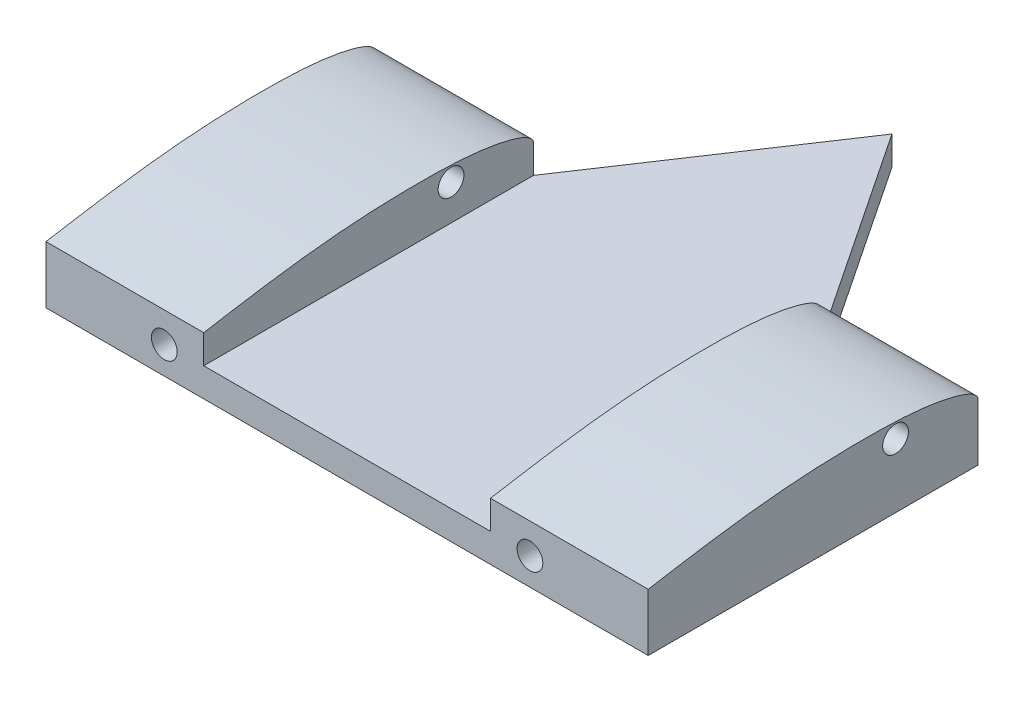
SolidWorks part; units mm, degrees
note: The reader was unsure of these and kept them because the rebuilt part matched: shared geometry of "Schizzo13<3>".
ref_plane "Piano frontale" through (0, 0, 0) normal (0, 0, 1) x (1, 0, 0)
ref_plane "Piano superiore" through (0, 0, 0) normal (0, 1, 0) x (1, 0, 0)
ref_plane "Piano destro" through (0, 0, 0) normal (1, 0, 0) x (0, 0, -1)
curve "Curva2"
  spline degree 3 poles (0, 0.1586, 228.4222) (0, -0.0487, 230.3931) (0, 0.2265, 228.4621) (0, 0.5086, 226.913) (0, 1.1462, 223.2123) (0, 1.931, 218.7267) (0, 2.9273, 212.8543) (0, 3.9498, 206.059) (0, 5.2727, 198.3155) (0, 6.561, 189.7964) (0, 7.9418, 180.47) (0, 9.3069, 170.5242) (0, 10.6253, 160.0699) (0, 11.8511, 149.2161) (0, 12.9346, 138.0666) (0, 13.8481, 126.7243) (0, 14.5595, 115.2867) (0, 15.0727, 103.8577) (0, 15.3886, 92.5492) (0, 15.5156, 81.4816) (0, 15.4486, 70.7769) (0, 15.1745, 60.5512) (0, 14.684, 50.9063) (0, 13.9467, 41.9272) (0, 12.97, 33.6788) (0, 11.7653, 26.2174) (0, 10.3812, 19.5949) (0, 8.87, 13.8689) (0, 7.2805, 9.0905) (0, 5.6287, 5.3083) (0, 3.8993, 2.5106) (0, 2.1212, 0.7476) (0, 0.7292, 0.0287) (0, -0.3776, -0.0196) (0, -1.5746, 0.4553) (0, -2.6365, 2.4153) (0, -3.7172, 5.2419) (0, -4.5344, 9.2662) (0, -5.1496, 14.3761) (0, -5.5312, 20.6192) (0, -5.7638, 27.933) (0, -5.8709, 36.2454) (0, -5.8469, 45.4468) (0, -5.721, 55.4256) (0, -5.4718, 66.0577) (0, -5.0939, 77.2256) (0, -4.5435, 88.8224) (0, -3.8205, 100.7584) (0, -2.962, 112.9458) (0, -2.0157, 125.2822) (0, -1.0562, 137.6465) (0, -0.1474, 149.8969) (0, 0.6495, 161.8774) (0, 1.2784, 173.4199) (0, 1.6866, 184.3415) (0, 1.8102, 194.4306) (0, 1.6774, 203.4894) (0, 1.3775, 211.306) (0, 0.9882, 217.8619) (0, 0.6308, 222.8142) (0, 0.284, 226.7967) (0, 0.1586, 228.4222) (0, -0.0487, 230.3931) (0, 0.2265, 228.4621) knots -0.014202 -0.006329 -0.001589 0 0.001576 0.006211 0.01368 0.023764 0.036307 0.051658 0.068045 0.086769 0.107053 0.128647 0.151303 0.174786 0.19886 0.223309 0.247929 0.272522 0.296848 0.320648 0.343669 0.365658 0.3864 0.405741 0.423561 0.439779 0.454311 0.467034 0.477831 0.486643 0.493542 0.498786 0.50271 0.50309 0.505896 0.510322 0.516831 0.525521 0.536535 0.549945 0.565696 0.583577 0.603379 0.624844 0.647727 0.671743 0.696673 0.722357 0.748609 0.77521 0.801891 0.828329 0.854175 0.879074 0.902636 0.924421 0.943939 0.960827 0.974827 0.985798 0.993671 0.998411 1 1.001576 1.006211 1.01368 periodic
sketch "Schizzo1" plane through (0, 0, 0) normal (1, 0, 0) x (0, 0, -1)
  spline S1 degree 3 poles (-228.4621, 0.2265) (-230.3931, -0.0487) (-228.4222, 0.1586) (-226.7967, 0.284) (-222.8142, 0.6308) (-217.8619, 0.9882) (-211.306, 1.3775) (-203.4894, 1.6774) (-194.4306, 1.8102) (-184.3415, 1.6866) (-173.4199, 1.2784) (-161.8774, 0.6495) (-149.8969, -0.1474) (-137.6465, -1.0562) (-125.2822, -2.0157) (-112.9458, -2.962) (-100.7584, -3.8205) (-88.8224, -4.5435) (-77.2256, -5.0939) (-66.0577, -5.4718) (-55.4256, -5.721) (-45.4468, -5.8469) (-36.2454, -5.8709) (-27.933, -5.7638) (-20.6192, -5.5312) (-14.3761, -5.1496) (-9.2662, -4.5344) (-5.2419, -3.7172) (-2.4153, -2.6365) (-0.4553, -1.5746) (0.0196, -0.3776) (-0.0287, 0.7292) (-0.7476, 2.1212) (-2.5106, 3.8993) (-5.3083, 5.6287) (-9.0905, 7.2805) (-13.8689, 8.87) (-19.5949, 10.3812) (-26.2174, 11.7653) (-33.6788, 12.97) (-41.9272, 13.9467) (-50.9063, 14.684) (-60.5512, 15.1745) (-70.7769, 15.4486) (-81.4816, 15.5156) (-92.5492, 15.3886) (-103.8577, 15.0727) (-115.2867, 14.5595) (-126.7243, 13.8481) (-138.0666, 12.9346) (-149.2161, 11.8511) (-160.0699, 10.6253) (-170.5242, 9.3069) (-180.47, 7.9418) (-189.7964, 6.561) (-198.3155, 5.2727) (-206.059, 3.9498) (-212.8543, 2.9273) (-218.7267, 1.931) (-223.2123, 1.1462) (-226.913, 0.5086) (-228.4621, 0.2265) (-230.3931, -0.0487) (-228.4222, 0.1586) knots -0.01368 -0.006211 -0.001576 0 0.001589 0.006329 0.014202 0.025173 0.039173 0.056061 0.075579 0.097364 0.120926 0.145825 0.171671 0.198109 0.22479 0.251391 0.277643 0.303327 0.328257 0.352273 0.375156 0.396621 0.416423 0.434304 0.450055 0.463465 0.474479 0.483169 0.489678 0.494104 0.49691 0.49729 0.501214 0.506458 0.513357 0.522169 0.532966 0.545689 0.560221 0.576439 0.594259 0.6136 0.634342 0.656331 0.679352 0.703152 0.727478 0.752071 0.776691 0.80114 0.825214 0.848697 0.871353 0.892947 0.913231 0.931955 0.948342 0.963693 0.976236 0.98632 0.993789 0.998424 1 1.001589 1.006329 1.014202 only from (-230, 0) to (-230, 0)
ref_plane "Piano1" through (100, 0, 0) normal (1, 0, 0) x (0, 0, -1)
sketch "Schizzo3" plane through (0, 0, 0) normal (0, 1, 0) x (1, 0, 0)
  line L0 (-100, 115) -> (0, 265)
  line L1 (-100, 115) -> (100, 115) construction
  line L2 (-100, 115) -> (-100, -115)
  line L3 (-100, -115) -> (100, -115)
  line L4 (100, 115) -> (100, -115)
  line L5 (-100, 115) -> (100, -115) construction
  line L6 (-100, -115) -> (100, 115) construction
  line L7 (0, 265) -> (100, 115)
  line L8 (0, 265) -> (0, 115) construction
  point P0 (0, 0)
  dimension "D1" = 200
  dimension "D2" = 230
  dimension "D3" = 150
extrude "Estrusione-Estrusione1" add sketch "Schizzo3" along normal blind 10
sketch "Schizzo4" plane through (0, 0, 0) normal (0, 1, 0) x (1, 0, 0)
  line L1 (-100, 115) -> (-210, 115)
  line L2 (-100, 115) -> (-100, -115)
  line L3 (-100, -115) -> (-210, -115)
  line L4 (-210, 115) -> (-210, -115)
  dimension "D1" = 110
extrude "Estrusione-Estrusione2" add sketch "Schizzo4" along normal blind 30
mirror "Specchia1" about plane through (0, 0, 0) normal (1, 0, 0) of "Estrusione-Estrusione2"
sketch "Schizzo2" plane through (100, 0, 0) normal (1, 0, 0) x (0, 0, -1)
  line L0 (-115, 30) -> (115, 30) construction
  line L1 (115, 30) -> (115, 38.7777) construction
  line L2 (115, 30) -> (115, 0) construction
  line L4 (115, 10) -> (115, 0) construction
  spline S0 degree 3 poles (-113.4621, 30.2264) (-115.3931, 29.9513) (-113.4221, 30.1585) (-111.7966, 30.2838) (-107.8142, 30.6303) (-102.8619, 30.9873) (-96.3059, 31.3762) (-88.4893, 31.6755) (-79.4305, 31.8077) (-69.3414, 31.6834) (-58.4199, 31.2745) (-46.8774, 30.6448) (-34.8969, 29.847) (-22.6466, 28.9374) (-10.2824, 27.9771) (2.054, 27.0298) (14.2412, 26.1705) (26.1772, 25.4467) (37.774, 24.8955) (48.9419, 24.5168) (59.5739, 24.2669) (69.5527, 24.1402) (78.7541, 24.1157) (87.0666, 24.2221) (94.3803, 24.4543) (100.6234, 24.8354) (105.7335, 25.4502) (109.7578, 26.2672) (112.5844, 27.3477) (114.5445, 28.4094) (115.0195, 29.6064) (114.9713, 30.7133) (114.2525, 32.1053) (112.4896, 33.8835) (109.692, 35.6131) (105.91, 37.2651) (101.1316, 38.855) (95.4058, 40.3666) (88.7834, 41.7511) (81.3221, 42.9564) (73.0737, 43.9336) (64.0947, 44.6716) (54.4498, 45.1628) (44.2242, 45.4376) (33.5194, 45.5052) (22.4518, 45.379) (11.1433, 45.0639) (-0.2857, 44.5515) (-11.7234, 43.841) (-23.0657, 42.9282) (-34.2153, 41.8454) (-45.0692, 40.6205) (-55.5235, 39.3028) (-65.4695, 37.9383) (-74.796, 36.5582) (-83.3152, 35.2705) (-91.0587, 33.9482) (-97.8541, 32.9261) (-103.7266, 31.9302) (-108.2122, 31.1457) (-111.9129, 30.5084) (-113.4621, 30.2264) (-115.3931, 29.9513) (-113.4221, 30.1585) knots -0.01368 -0.006211 -0.001576 0 0.001589 0.006329 0.014202 0.025173 0.039173 0.056061 0.075579 0.097364 0.120926 0.145825 0.171671 0.198109 0.22479 0.251391 0.277643 0.303327 0.328257 0.352273 0.375156 0.396621 0.416423 0.434304 0.450055 0.463465 0.474479 0.483169 0.489678 0.494104 0.49691 0.49729 0.501214 0.506458 0.513357 0.522169 0.532966 0.545689 0.560221 0.576439 0.594259 0.6136 0.634342 0.656331 0.679352 0.703152 0.727478 0.752071 0.776691 0.80114 0.825214 0.848697 0.871353 0.892947 0.913231 0.931955 0.948342 0.963693 0.976236 0.98632 0.993789 0.998424 1 1.001589 1.006329 1.014202 only from (-115, 30) to (-115, 30)
  point P5 (-115, 30)
  dimension "D1" = 30
  dimension "D2" = 230
other "Schizzo a penna1" parameters "D1"=57.9231, "D2"=109.7502
sketch "Schizzo7" plane through (210, 0, 0) normal (1, 0, 0) x (0, 0, -1)
  line L0 (-115, 30) -> (-67.1161, 36.7044)
  line L1 (-67.1161, 36.7044) -> (-28.0456, 30)
  line L2 (-115, 30) -> (115, 30) construction
  line L3 (-28.0456, 30) -> (-115, 30)
  line L4 (-67.1161, 36.7044) -> (-67.1161, 30) construction
  dimension "D1" = 6.7044
  dimension "D2" = 86.9544
extrude "Estrusione-Estrusione6" add sketch "Schizzo7" against normal blind 110
extrude "Estrusione-Estrusione7" add sketch "Schizzo2" along normal blind 110 contours S0
mirror "Specchia2" about plane through (0, 0, 0) normal (1, 0, 0) of "Estrusione-Estrusione7", "Estrusione-Estrusione6"
sketch "Schizzo12" plane through (100, 0, 0) normal (1, 0, 0) x (0, 0, -1)
  line L0 (115, 30) -> (57.5, 34.6592) construction
  line L1 (57.5, 34.6592) -> (57.5, 30) construction
  line L2 (-115, 30) -> (115, 30) construction
  line L3 (57.5, 30) -> (115, 30) construction
  line L4 (57.5, 24.3254) -> (57.5, 44.9929) construction
  circle A0 centre (57.5, 34.6592) radius 9
  spline S1 degree 3 poles (-113.4621, 30.2264) (-115.3931, 29.9513) (-113.4221, 30.1585) (-111.7966, 30.2838) (-107.8142, 30.6303) (-102.8619, 30.9873) (-96.3059, 31.3762) (-88.4893, 31.6755) (-79.4305, 31.8077) (-69.3414, 31.6834) (-58.4199, 31.2745) (-46.8774, 30.6448) (-34.8969, 29.847) (-22.6466, 28.9374) (-10.2824, 27.9771) (2.054, 27.0298) (14.2412, 26.1705) (26.1772, 25.4467) (37.774, 24.8955) (48.9419, 24.5168) (59.5739, 24.2669) (69.5527, 24.1402) (78.7541, 24.1157) (87.0666, 24.2221) (94.3803, 24.4543) (100.6234, 24.8354) (105.7335, 25.4502) (109.7578, 26.2672) (112.5844, 27.3477) (114.5445, 28.4094) (115.0195, 29.6064) (114.9713, 30.7133) (114.2525, 32.1053) (112.4896, 33.8835) (109.692, 35.6131) (105.91, 37.2651) (101.1316, 38.855) (95.4058, 40.3666) (88.7834, 41.7511) (81.3221, 42.9564) (73.0737, 43.9336) (64.0947, 44.6716) (54.4498, 45.1628) (44.2242, 45.4376) (33.5194, 45.5052) (22.4518, 45.379) (11.1433, 45.0639) (-0.2857, 44.5515) (-11.7234, 43.841) (-23.0657, 42.9282) (-34.2153, 41.8454) (-45.0692, 40.6205) (-55.5235, 39.3028) (-65.4695, 37.9383) (-74.796, 36.5582) (-83.3152, 35.2705) (-91.0587, 33.9482) (-97.8541, 32.9261) (-103.7266, 31.9302) (-108.2122, 31.1457) (-111.9129, 30.5084) (-113.4621, 30.2264) (-115.3931, 29.9513) (-113.4221, 30.1585) knots -0.01368 -0.006211 -0.001576 0 0.001589 0.006329 0.014202 0.025173 0.039173 0.056061 0.075579 0.097364 0.120926 0.145825 0.171671 0.198109 0.22479 0.251391 0.277643 0.303327 0.328257 0.352273 0.375156 0.396621 0.416423 0.434304 0.450055 0.463465 0.474479 0.483169 0.489678 0.494104 0.49691 0.49729 0.501214 0.506458 0.513357 0.522169 0.532966 0.545689 0.560221 0.576439 0.594259 0.6136 0.634342 0.656331 0.679352 0.703152 0.727478 0.752071 0.776691 0.80114 0.825214 0.848697 0.871353 0.892947 0.913231 0.931955 0.948342 0.963693 0.976236 0.98632 0.993789 0.998424 1 1.001589 1.006329 1.014202 only from (-115, 30) to (-115, 30) construction
  point P13 (57.5, 34.6592)
  dimension "D2" = 18
  dimension "D1" = 57.5
extrude "Taglio-Estrusione1" cut sketch "Schizzo12" against normal through all and the other way through all
sketch "Schizzo13" plane through (0, 0, 115) normal (0, 0, 1) x (1, 0, 0)
  line L0 (-182.5, 9) -> (-155, 9) construction
  line L1 (-210, 9) -> (-182.5, 9) construction
  line L3 (-155, 30) -> (-155, 9) construction
  line L4 (-210, 30) -> (-100, 30) construction
  line L5 (-155, 9) -> (-127.5, 9) construction
  line L6 (-210, 0) -> (210, 0) construction
  line L7 (-210, 30) -> (-210, 0) construction
  circle A0 centre (-182.5, 9) radius 9
  circle A1 centre (-127.5, 9) radius 9
  dimension "D1" = 18
sketch "Schizzo14" plane through (0, 0, 0) normal (0, -1, 0) x (1, 0, 0)
  line L0 (-210, 115) -> (210, 115)
  line L1 (210, 115) -> (210, -115)
  line L2 (210, -115) -> (100, -115)
  line L3 (100, -115) -> (210, -115) construction
  line L4 (100, -115) -> (0, -265)
  line L5 (100, -115) -> (0, -265) construction
  line L6 (0, -265) -> (-100, -115)
  line L7 (-100, -115) -> (-210, -115)
  line L8 (-210, -115) -> (-210, 115)
extrude "Estrusione-Estrusione8" add sketch "Schizzo14" along normal blind 10
extrude "Taglio-Estrusione2" cut sketch "Schizzo13" against normal blind 210 contours A1
extrude "Taglio-Estrusione3" cut sketch "Schizzo13<3>" against normal blind 210 from offset 20 contours A0 offset against normal yes
sketch "Schizzo13<3>" plane through (0, 0, 115) normal (0, 0, 1) x (1, 0, 0) same geometry as "Schizzo13"
mirror "Specchia3" about plane through (0, 0, 0) normal (1, 0, 0) of "Taglio-Estrusione3", "Taglio-Estrusione2"
